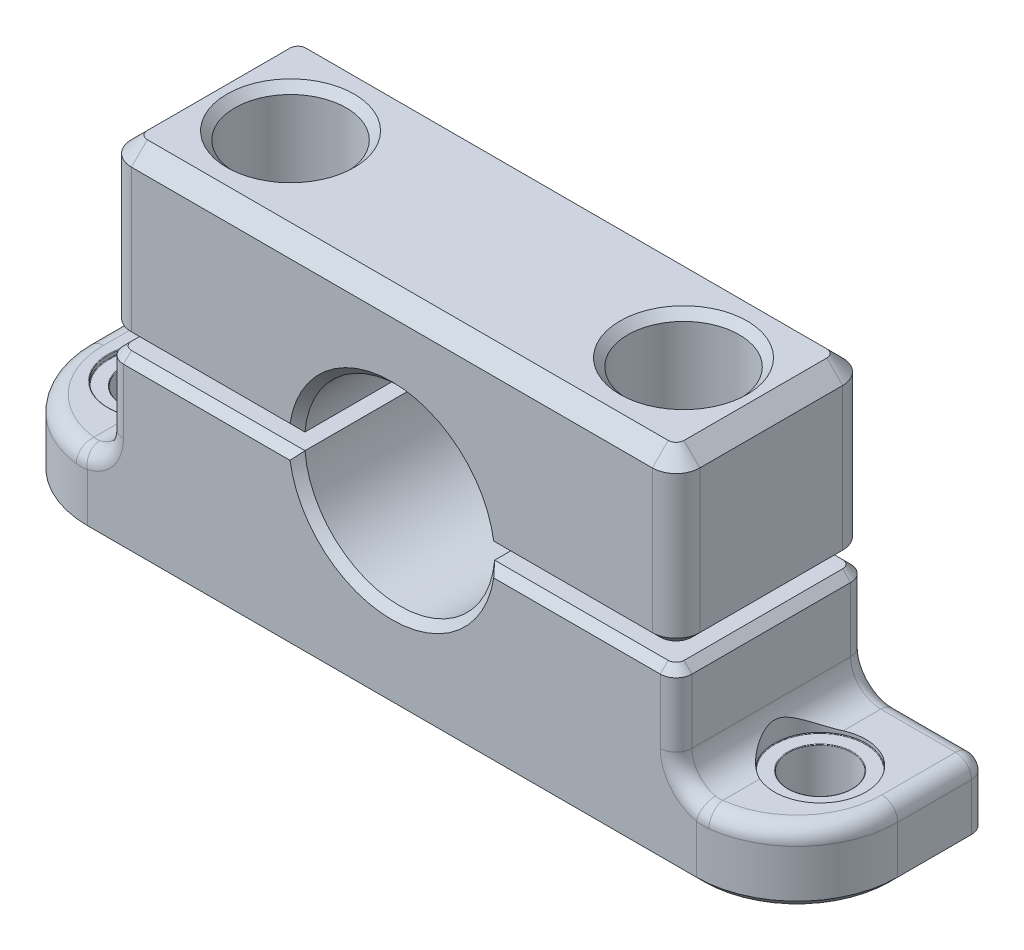
SolidWorks part; units mm, degrees
note: '?' marks a value the reader was unsure of.
material "ABS"
ref_plane "Front" through (0, 0, 0) normal (0, 0, 1) x (1, 0, 0)
ref_plane "Top" through (0, 0, 0) normal (0, 1, 0) x (1, 0, 0)
ref_plane "Right" through (0, 0, 0) normal (1, 0, 0) x (0, 0, -1)
sketch "Sketch1" plane through (0, 0, 0) normal (0, 0, 1) x (1, 0, 0)
  line L0 (0, 22.46) -> (0, 0) construction
  line L1 (-25.54, 0) -> (25.54, 0) construction
  line L2 (0, 0) -> (0, 11.46) construction
  line L3 (-21, 0) -> (21, 0) construction
  line L4 (19, 0) -> (23, 0) construction
  line L5 (23, 0) -> (23, 1.27) construction
  line L6 (19, 0) -> (19, 1.27) construction
  line L7 (-19, 0) -> (-19, 1.27) construction
  line L8 (-23, 0) -> (-23, 1.27) construction
  line L9 (-19, 0) -> (-23, 0) construction
  line L10 (-17.92, 11.46) -> (17.92, 11.46) construction
  line L11 (-17.92, 10.952) -> (17.92, 10.952) construction
  line L12 (-17.92, 11.968) -> (17.92, 11.968) construction
  line L13 (18.5, 0) -> (18.5, 1.27) construction
  line L14 (23.5, 0) -> (23.5, 1.27) construction
  line L15 (-18.5, 0) -> (-18.5, 1.27) construction
  line L16 (-23.5, 0) -> (-23.5, 1.27) construction
  line L17 (-11.0713, 10.952) -> (11.0713, 10.952) construction
  line L18 (-11.0713, 11.968) -> (11.0713, 11.968) construction
  line L19 (-11.0713, 11.46) -> (11.0713, 11.46) construction
  line L20 (-25.54, 0) -> (-25.54, 4.492) construction
  line L21 (-25.54, 4.492) -> (-17.92, 4.492) construction
  line L22 (-17.92, 10.952) -> (-17.92, 4.492) construction
  line L23 (-17.92, 11.968) -> (-17.92, 22.46) construction
  line L24 (-17.92, 22.46) -> (17.92, 22.46) construction
  line L25 (25.54, 0) -> (25.54, 4.492) construction
  line L26 (25.54, 4.492) -> (17.92, 4.492) construction
  line L27 (17.92, 10.952) -> (17.92, 4.492) construction
  line L28 (17.92, 11.968) -> (17.92, 22.46) construction
  line L29 (0, 22.46) -> (0, 15.46) construction
  line L30 (0.3175, 15.46) -> (-0.3175, 15.46) construction
  line L31 (17.92, 4.492) -> (17.92, 0) construction
  circle A0 centre (0, 11.46) radius 6 construction
  arc A1 (-19.825, 4.492) -> (-17.92, 6.397) centre (-19.825, 6.397) ccw construction
  arc A2 (19.825, 4.492) -> (17.92, 6.397) centre (19.825, 6.397) cw construction
  point P5 (0, 0)
  point P9 (0, 11.46)
  point P11 (0, 0)
  point P12 (21, 0)
  point P13 (-21, 0)
  point P16 (21, 0)
  point P37 (0, 10.952)
  point P40 (0, 11.968)
  point P60 (0, 15.46)
  point P64 (21.73, 4.492)
  dimension "D1" = 1.27
  dimension "D8" = 4.492
  dimension "D12" = 0.635
  dimension "D10" = 1.905
  dimension "D11" = 1.905
  dimension "D9" = 4.54
  dimension "D13" = 3.08
  dimension "D2" = 0.508
  dimension "D3" = 0.508
  dimension "D4" = 0.5
  dimension "D5" = 0.5
  dimension "D6" = 0.5
  dimension "D7" = 0.5
sketch "Sketch3" plane through (0, 0, 0) normal (0, 0, 1) x (1, 0, 0)
  line L0 (-17.92, 22.46) -> (17.92, 22.46) construction
  line L1 (17.92, 11.968) -> (17.92, 22.46) construction
  line L2 (-17.92, 11.968) -> (17.92, 11.968) construction
  line L3 (-17.92, 11.968) -> (-17.92, 22.46) construction
  line L4 (-17.92, 10.952) -> (-17.92, 4.492) construction
  line L5 (-25.54, 4.492) -> (-17.92, 4.492) construction
  line L6 (-25.54, 0) -> (-25.54, 4.492) construction
  line L7 (-25.54, 0) -> (25.54, 0) construction
  line L8 (25.54, 0) -> (25.54, 4.492) construction
  line L9 (25.54, 4.492) -> (17.92, 4.492) construction
  line L10 (17.92, 10.952) -> (17.92, 4.492) construction
  line L11 (-17.92, 10.952) -> (17.92, 10.952) construction
  line L12 (-17.92, 22.46) -> (17.92, 22.46)
  line L13 (17.92, 11.968) -> (17.92, 22.46)
  line L14 (-17.92, 11.968) -> (-5.9785, 11.968)
  line L15 (-17.92, 11.968) -> (-17.92, 22.46)
  line L16 (-17.92, 10.952) -> (-17.92, 6.397)
  line L17 (-25.54, 4.492) -> (-19.825, 4.492)
  line L18 (-25.54, 0) -> (-25.54, 4.492)
  line L19 (-25.54, 0) -> (25.54, 0)
  line L20 (25.54, 0) -> (25.54, 4.492)
  line L21 (25.54, 4.492) -> (19.825, 4.492)
  line L22 (17.92, 10.952) -> (17.92, 6.397)
  line L23 (-17.92, 10.952) -> (-5.9785, 10.952)
  line L24 (5.9785, 11.968) -> (17.92, 11.968)
  line L25 (5.9785, 10.952) -> (17.92, 10.952)
  arc A0 (-19.825, 4.492) -> (-17.92, 6.397) centre (-19.825, 6.397) ccw construction
  arc A1 (17.92, 6.397) -> (19.825, 4.492) centre (19.825, 6.397) ccw construction
  circle A2 centre (0, 11.46) radius 6 construction
  arc A3 (-19.825, 4.492) -> (-17.92, 6.397) centre (-19.825, 6.397) ccw
  arc A4 (17.92, 6.397) -> (19.825, 4.492) centre (19.825, 6.397) ccw
  arc A5 (5.9785, 11.968) -> (-5.9785, 11.968) centre (0, 11.46) ccw
  arc A6 (-5.9785, 10.952) -> (5.9785, 10.952) centre (0, 11.46) ccw
extrude "Boss-Extrude1" add sketch "Sketch3" against normal blind 12
sketch "Sketch4" plane through (0, 0, 0) normal (0, -1, 0) x (1, 0, 0)
  line L0 (-25.54, 0) -> (-25.54, -12) construction
  line L1 (-25.54, 0) -> (-17.92, 0) construction
  line L2 (-25.54, -6) -> (25.54, -6) construction
  line L3 (25.54, -12) -> (25.54, 0) construction
  line L4 (-21, 0) -> (-21, -12) construction
  line L5 (21, 0) -> (21, -12) construction
  line L6 (-25.54, -12) -> (25.54, -12) construction
  line L7 (0, 0) -> (0, -12) construction
  circle A0 centre (-21, -6) radius 2
  circle A1 centre (21, -6) radius 2
  point P7 (-25.54, -6)
  dimension "D1" = 4
extrude "Cut-Extrude1" cut sketch "Sketch4" against normal through all
sketch "Sketch6" plane through (0, 4.492, 0) normal (0, 1, 0) x (1, 0, 0)
  line L0 (0, 0) -> (0, 12) construction
  line L1 (-25.54, 0) -> (25.54, 0) construction
  line L2 (17.92, 12) -> (-17.92, 12) construction
  circle A1 centre (-21, 6) radius 2 construction
  circle A2 centre (-21, 6) radius 2
  circle A4 centre (-21, 6) radius 2.381
  circle A5 centre (21, 6) radius 2.381
  dimension "D1" = 0.381
sketch "Sketch7" plane through (0, 0, 0) normal (0, 0, 1) x (1, 0, 0)
  line L0 (-25.54, 4.238) -> (25.54, 4.238) construction
  line L1 (-17.92, 10.952) -> (-17.92, 0) construction
  line L2 (-25.54, 0) -> (25.54, 0) construction
  line L3 (17.92, 10.952) -> (17.92, 0) construction
  line L5 (-25.54, 0) -> (-25.54, 4.492) construction
  line L6 (-25.54, 4.492) -> (-17.92, 4.492) construction
  line L7 (25.54, 0) -> (25.54, 4.492) construction
  line L8 (-21, 4.492) -> (-21, 4.238) construction
  line L9 (21, 4.492) -> (21, 4.238) construction
  line L10 (25.54, 4.492) -> (17.92, 4.492) construction
  dimension "D1" = 0.254
sketch "Sketch8" plane through (0, 10.952, 0) normal (0, 1, 0) x (1, 0, 0)
  line L0 (0, 0) -> (0, 12) construction
  line L1 (17.92, 12) -> (-17.92, 12) construction
  circle A0 centre (-21, 6) radius 2.381 construction
  circle A1 centre (21, 6) radius 2.381 construction
  circle A2 centre (-21, 6) radius 2.381 construction
  circle A3 centre (21, 6) radius 2.381 construction
  circle A4 centre (-21, 6) radius 2.881
  circle A5 centre (21, 6) radius 2.881
  dimension "D1" = 0.5
extrude "Cut-Extrude3" cut sketch "Sketch8" against normal up to vertex (6.714 mm away) up to point (-21, 4.238, 0)
sketch "Sketch10" plane through (0, 22.46, 0) normal (0, 1, 0) x (1, 0, 0)
  line L0 (-17.92, 12) -> (-17.92, 0) construction
  line L1 (17.92, 12) -> (17.92, 0) construction
  line L2 (-17.92, 12) -> (-17.92, 0) construction
  line L3 (17.92, 12) -> (17.92, 0) construction
  line L4 (-15.888, 12) -> (-15.888, 0) construction
  line L5 (0, 0) -> (0, 12) construction
  line L6 (15.888, 12) -> (15.888, 0) construction
  circle A0 centre (-12.388, 6) radius 2 construction
  circle A1 centre (12.388, 6) radius 2.254
  circle A2 centre (-12.388, 6) radius 2.254
  circle A3 centre (12.388, 6) radius 2 construction
  circle A4 centre (-12.388, 6) radius 3.5 construction
  circle A5 centre (12.388, 6) radius 3.5 construction
  dimension "D1" = 2.032
  dimension "D3" = 0.254
extrude "Cut-Extrude4" cut sketch "Sketch10" against normal through all
ref_plane "Plane1" through (0, 0, -6) normal (0, 0, 1) x (1, 0, 0)
sketch "Sketch12" plane through (0, 22.46, 0) normal (0, 1, 0) x (1, 0, 0)
  line L0 (0, 12) -> (0, 0) construction
  circle A0 centre (-12.388, 6) radius 3.3855 construction
  circle A1 centre (12.388, 6) radius 3.5125
  circle A2 centre (-12.388, 6) radius 3.5125
  circle A3 centre (12.388, 6) radius 3.3855 construction
  dimension "D2" = 7.025
extrude "Cut-Extrude5" cut sketch "Sketch12" against normal blind 7.015
sketch "Sketch13" plane through (0, 0, 0) normal (0, 1, 0) x (1, 0, 0)
  line L0 (-12.388, 12) -> (-12.388, 0) construction
  line L1 (17.92, 12) -> (-17.92, 12) construction
  line L2 (0, 12) -> (0, 0) construction
  line L3 (12.388, 12) -> (12.388, 0) construction
  circle A0 centre (-12.388, 6) radius 2.0066 construction
  point P2 (-12.388, 6)
  point P9 (-12.388, 12)
  point P10 (-12.388, 0)
  point P17 (12.388, 12)
  point P18 (12.388, 0)
  dimension "D1" = 4.0132
sketch "Sketch15" plane through (0, 0, -6) normal (0, 0, 1) x (1, 0, 0)
  line L0 (-12.388, 4.238) -> (-12.388, 22.46) construction
  line L1 (-12.388, 22.46) -> (-15.888, 22.46) construction
  line L2 (-15.888, 22.46) -> (-15.888, 15.46) construction
  line L3 (-15.888, 15.46) -> (-14.388, 15.46) construction
  line L4 (-14.388, 15.46) -> (-14.388, 4.238) construction
  line L5 (-14.388, 4.238) -> (-12.388, 4.238) construction
  line L6 (-25.54, 4.238) -> (25.54, 4.238) construction
  line L8 (-17.92, 22.46) -> (17.92, 22.46) construction
  line L9 (-12.388, 4.238) -> (-12.388, 22.46)
  line L10 (-12.388, 22.46) -> (-15.888, 22.46)
  line L11 (-15.888, 22.46) -> (-15.888, 15.46)
  line L12 (-15.888, 15.46) -> (-14.388, 15.46)
  line L13 (-14.388, 15.46) -> (-14.388, 4.238)
  line L14 (-14.388, 4.238) -> (-12.388, 4.238)
  dimension "D2" = 3.5
  dimension "D1" = 7
  dimension "D3" = 2
revolve "Revolve1" [suppressed] add sketch "Sketch15" angle 360 about L9
chamfer "Chamfer1" [suppressed] distance 0.127 angle 45
sketch "Sketch16" [suppressed] plane through (0, 25, 0) normal (0, 1, 0) x (1, 0, 0)
  line L0 (-10.468, 12) -> (-10.468, 0) construction
  line L1 (-10.468, 7.7321) -> (-11.968, 6.866)
  line L2 (-11.968, 6.866) -> (-11.968, 5.134)
  line L3 (-11.968, 5.134) -> (-10.468, 4.2679)
  line L4 (-10.468, 4.2679) -> (-8.968, 5.134)
  line L5 (-8.968, 5.134) -> (-8.968, 6.866)
  line L6 (-8.968, 6.866) -> (-10.468, 7.7321)
  circle A0 centre (-10.468, 6) radius 1.5 construction
  dimension "Hex Size" = 3
extrude "Cut-Extrude6" [suppressed] cut sketch "Sketch16" against normal blind 2.31
mirror "Mirror1" [suppressed] about plane through (0, 0, 0) normal (1, 0, 0)
fillet "Fillet1" radius 1.5 4 edges at (-17.92, 17.214, -12) (-17.92, 17.214, 0) (17.92, 17.214, -12) (17.92, 17.214, 0)
chamfer "Chamfer3" distance 1 angle 45 8 edges at (0, 22.46, -12) (17.4807, 22.46, -11.5607) (-17.4807, 22.46, -11.5607) (17.92, 22.46, -6) (-17.92, 22.46, -6) (17.4807, 22.46, -0.4393) (-17.4807, 22.46, -0.4393) (0, 22.46, 0)
fillet "Fillet4" radius 6.35 2 edges at (25.54, 2.246, 0) (-25.54, 2.246, 0)
fillet "Fillet2" radius 1 18 edges at (22.6825, 4.492, -12) (18.478, 5.05, -12) (17.92, 8.6745, 0) (18.2696, 5.2971, 0) (-18.2696, 5.2971, 0) (-22.6825, 4.492, -12) (-18.478, 5.05, -12) (17.92, 8.6745, -12) (25.54, 2.246, -12) (25.54, 4.492, -9.175) (-25.54, 2.246, -12) (-25.54, 4.492, -9.175) (-17.92, 8.6745, 0) (-17.92, 8.6745, -12) (23.8993, 4.492, -2.0903) (-23.8993, 4.492, -2.0903)
chamfer "Chamfer4" distance 0.5 angle 45 20 edges at (0, 0, -12) (-25.54, 0, -8.675) (-23.6801, 0, -1.8599) (0, 0, 0) (23.6801, 0, -1.8599) (25.54, 0, -8.675) (11.4492, 10.952, 0) (-11.4492, 10.952, 0) (17.6271, 10.952, -0.2929) (-17.6271, 10.952, -0.2929) (17.92, 10.952, -6) (-17.92, 10.952, -6) (17.6271, 10.952, -11.7071) (-17.6271, 10.952, -11.7071) (11.4492, 10.952, -12) (-11.4492, 10.952, -12) (0, 5.46, -12) (0, 5.46, 0) (25.2471, 0, -11.7071) (-25.2471, 0, -11.7071)
fillet "Fillet3" radius 0.0381 6 edges at (-23.881, 4.238, -6) (23.881, 4.238, -6) (23, 4.238, -6) (-18.1195, 5.5483, -6.0547) (-23.881, 4.492, -6) (-23, 4.238, -6)
chamfer "Chamfer2" distance 0.5 angle 45 4 edges at (14.642, 15.445, -6) (15.9005, 22.46, -6) (-14.642, 15.445, -6) (-15.9005, 22.46, -6)
chamfer "Chamfer5" distance 0.5 angle 45 12 edges at (0, 17.46, -12) (-11.1992, 11.968, -12) (11.1992, 11.968, -12) (-17.4807, 11.968, -11.5607) (17.4807, 11.968, -11.5607) (-17.92, 11.968, -6) (17.92, 11.968, -6) (-17.4807, 11.968, -0.4393) (17.4807, 11.968, -0.4393) (-11.1992, 11.968, 0) (11.1992, 11.968, 0) (0, 17.46, 0)
sketch "Sketch17" plane through (0, 0, 0) normal (0, 0, 1) x (1, 0, 0)
  line L0 (0, 22.46) -> (0, 0) construction
  line L2 (-17.92, 11.23) -> (17.92, 11.23) construction
  line L3 (-17.92, 6.397) -> (-17.92, 10.452) construction
  line L4 (17.92, 10.452) -> (17.92, 6.397) construction
  line L5 (16.4005, 22.46) -> (8.3755, 22.46) construction
  point P7 (0, 11.23)
ref_axis "Center Axis 1" through (0, 11.46, -11.5) along (0, 0, 1)?
ref_plane "Split Plane" through (0, 11.46, 0) normal (0, 1, 0) x (1, 0, 0)
ref_plane "Center Plane" through (0, 0, -6) normal (0, 0, 1) x (1, 0, 0)
ref_point "Origin Base"
split "Split1" trim tools "Split Plane" bodies to split 117 118 resulting bodies 132 133
equation "\"D8@Sketch1\"=\"Oall Ht@Sketch1\"*.20"
equation "\"D1@Sketch4\"= \"HoldDia@Sketch1\""
equation "\"D1@Cut-Extrude5\"=\"HeadDp@Sketch1\"+.015"
equation "\"D1@Sketch15\"=\"HeadDp@Sketch1\""
equation "\"D3@Sketch15\"=\"ThrdDia@Sketch10\"*.5"
equation "\"D1@Cut-Extrude6\"= \"HeadDp@Sketch1\"*.33"
equation "\"D2@Sketch12\"=\"Head Dia@Sketch10\"+.025"
equation "\"D2@Sketch15\"=\"Head Dia@Sketch10\"*.50"
